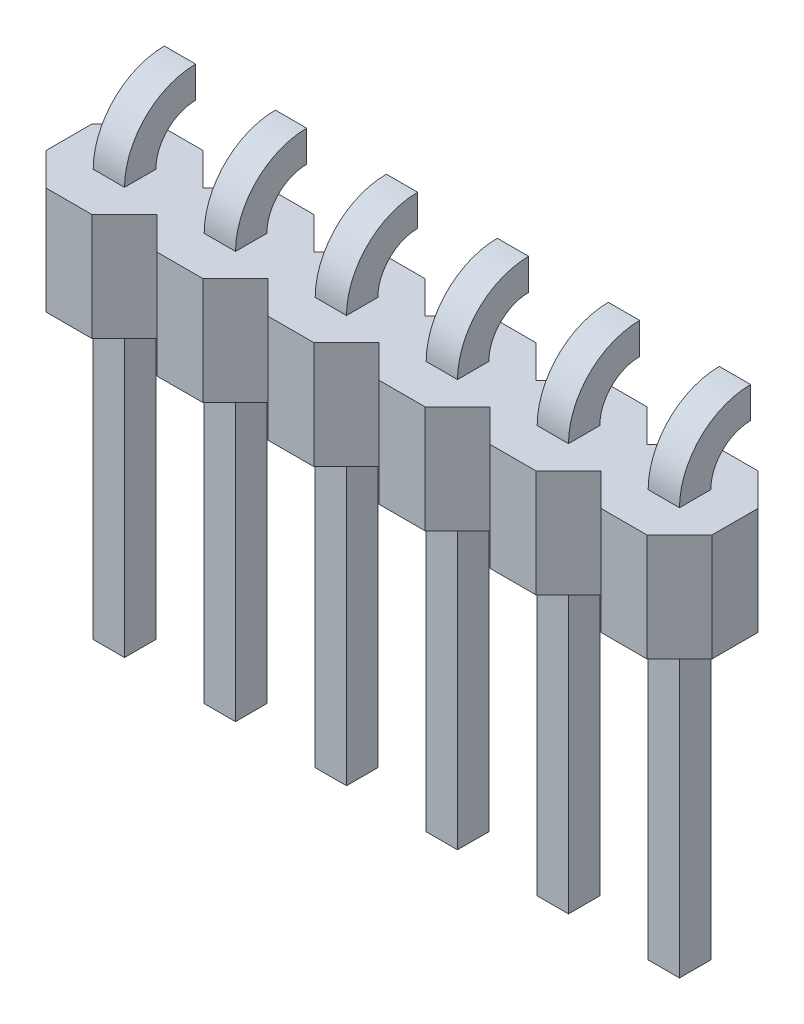
SolidWorks part; units mm, degrees
ref_plane "Front Plane" through (0, 0, 0) normal (0, 0, 1) x (1, 0, 0)
ref_plane "Top Plane" through (0, 0, 0) normal (0, 1, 0) x (1, 0, 0)
ref_plane "Right Plane" through (0, 0, 0) normal (1, 0, 0) x (0, 0, -1)
sketch "Sketch1" plane through (0, 0, 0) normal (0, 1, 0) x (1, 0, 0)
  line L0 (2.83, -0.35) -> (2.83, 0.35)
  line L1 (-0.35, -0.35) -> (0.35, -0.35)
  line L2 (-0.35, -0.35) -> (-0.35, 0.35)
  line L3 (-0.35, 0.35) -> (0.35, 0.35)
  line L4 (0.35, -0.35) -> (0.35, 0.35)
  line L5 (-0.35, -0.35) -> (0.35, 0.35) construction
  line L6 (-0.35, 0.35) -> (0.35, -0.35) construction
  line L7 (2.13, 0.35) -> (2.83, 0.35)
  line L8 (2.13, -0.35) -> (2.13, 0.35)
  line L9 (2.13, -0.35) -> (2.83, -0.35)
  line L10 (5.31, -0.35) -> (5.31, 0.35)
  line L11 (4.61, 0.35) -> (5.31, 0.35)
  line L12 (4.61, -0.35) -> (4.61, 0.35)
  line L13 (4.61, -0.35) -> (5.31, -0.35)
  line L14 (7.79, -0.35) -> (7.79, 0.35)
  line L15 (7.09, 0.35) -> (7.79, 0.35)
  line L16 (7.09, -0.35) -> (7.09, 0.35)
  line L17 (7.09, -0.35) -> (7.79, -0.35)
  line L18 (10.27, -0.35) -> (10.27, 0.35)
  line L19 (9.57, 0.35) -> (10.27, 0.35)
  line L20 (9.57, -0.35) -> (9.57, 0.35)
  line L21 (9.57, -0.35) -> (10.27, -0.35)
  line L22 (12.75, -0.35) -> (12.75, 0.35)
  line L23 (12.05, 0.35) -> (12.75, 0.35)
  line L24 (12.05, -0.35) -> (12.05, 0.35)
  line L25 (12.05, -0.35) -> (12.75, -0.35)
  point P0 (0, 0)
  dimension "D1" = 0.7
  dimension "D2" = 0.7
  dimension "D4" = 1.78
  dimension "D3" = 6
extrude "Boss-Extrude1" add sketch "Sketch1" along normal blind 9.1
sketch "Sketch3" plane through (0, 9.1, 0) normal (0, 1, 0) x (1, 0, 0)
  line L0 (-0.5136, 1.24) -> (-1.24, 0.5136)
  line L1 (-0.35, -0.35) -> (0.35, -0.35)
  line L2 (-0.35, -0.35) -> (-0.35, 0.35)
  line L3 (-0.35, 0.35) -> (0.35, 0.35)
  line L4 (0.35, -0.35) -> (0.35, 0.35)
  line L5 (-0.35, -0.35) -> (0.35, 0.35) construction
  line L6 (-0.35, 0.35) -> (0.35, -0.35) construction
  line L7 (-1.24, -0.5136) -> (-0.5136, -1.24)
  line L8 (-0.5136, -1.24) -> (0.5136, -1.24)
  line L9 (0.5136, -1.24) -> (1.24, -0.5136)
  line L10 (1.24, -0.5136) -> (1.24, 0.5136)
  line L11 (1.24, 0.5136) -> (0.5136, 1.24)
  line L12 (0.5136, 1.24) -> (-0.5136, 1.24)
  line L13 (-1.24, 0.5136) -> (-1.24, -0.5136)
  line L14 (2.83, 0.35) -> (2.13, -0.35) construction
  line L15 (2.83, -0.35) -> (2.13, 0.35) construction
  line L16 (3.72, -0.5136) -> (3.72, 0.5136)
  line L17 (2.9936, -1.24) -> (3.72, -0.5136)
  line L18 (2.83, 0.35) -> (2.13, 0.35)
  line L19 (2.13, 0.35) -> (2.13, -0.35)
  line L20 (2.13, -0.35) -> (2.83, -0.35)
  line L21 (2.83, -0.35) -> (2.83, 0.35)
  line L22 (2.83, 0.35) -> (2.13, 0.35) construction
  line L23 (2.13, 0.35) -> (2.13, -0.35) construction
  line L24 (2.13, -0.35) -> (2.83, -0.35) construction
  line L25 (2.83, -0.35) -> (2.83, 0.35) construction
  line L26 (1.9664, -1.24) -> (2.9936, -1.24)
  line L27 (1.24, -0.5136) -> (1.9664, -1.24)
  line L28 (1.24, 0.5136) -> (1.24, -0.5136)
  line L29 (1.9664, 1.24) -> (1.24, 0.5136)
  line L30 (2.9936, 1.24) -> (1.9664, 1.24)
  line L31 (3.72, 0.5136) -> (2.9936, 1.24)
  line L32 (6.2, -0.5136) -> (6.2, 0.5136)
  line L33 (5.4736, -1.24) -> (6.2, -0.5136)
  line L34 (4.4464, -1.24) -> (5.4736, -1.24)
  line L35 (3.72, -0.5136) -> (4.4464, -1.24)
  line L36 (3.72, 0.5136) -> (3.72, -0.5136)
  line L37 (4.4464, 1.24) -> (3.72, 0.5136)
  line L38 (5.4736, 1.24) -> (4.4464, 1.24)
  line L39 (6.2, 0.5136) -> (5.4736, 1.24)
  line L40 (8.68, -0.5136) -> (8.68, 0.5136)
  line L41 (7.9536, -1.24) -> (8.68, -0.5136)
  line L42 (6.9264, -1.24) -> (7.9536, -1.24)
  line L43 (6.2, -0.5136) -> (6.9264, -1.24)
  line L44 (6.2, 0.5136) -> (6.2, -0.5136)
  line L45 (6.9264, 1.24) -> (6.2, 0.5136)
  line L46 (7.9536, 1.24) -> (6.9264, 1.24)
  line L47 (8.68, 0.5136) -> (7.9536, 1.24)
  line L48 (11.16, -0.5136) -> (11.16, 0.5136)
  line L49 (10.4336, -1.24) -> (11.16, -0.5136)
  line L50 (9.4064, -1.24) -> (10.4336, -1.24)
  line L51 (8.68, -0.5136) -> (9.4064, -1.24)
  line L52 (8.68, 0.5136) -> (8.68, -0.5136)
  line L53 (9.4064, 1.24) -> (8.68, 0.5136)
  line L54 (10.4336, 1.24) -> (9.4064, 1.24)
  line L55 (11.16, 0.5136) -> (10.4336, 1.24)
  line L56 (13.64, -0.5136) -> (13.64, 0.5136)
  line L57 (12.9136, -1.24) -> (13.64, -0.5136)
  line L58 (11.8864, -1.24) -> (12.9136, -1.24)
  line L59 (11.16, -0.5136) -> (11.8864, -1.24)
  line L60 (11.16, 0.5136) -> (11.16, -0.5136)
  line L61 (11.8864, 1.24) -> (11.16, 0.5136)
  line L62 (12.9136, 1.24) -> (11.8864, 1.24)
  line L63 (13.64, 0.5136) -> (12.9136, 1.24)
  circle A0 centre (0, 0) radius 1.24 construction
  point P0 (0, 0)
  line M16 (12.75, 0.35) -> (12.05, 0.35)
  line M17 (12.05, 0.35) -> (12.05, -0.35)
  line M18 (12.05, -0.35) -> (12.75, -0.35)
  line M19 (12.75, -0.35) -> (12.75, 0.35)
  dimension "D1" = 0.7
  dimension "D2" = 0.7
  dimension "D4" = 1.24
  dimension "D3" = 0
  dimension "D5" = 6
extrude "Yükseklik-Ekstrüzyon1" add sketch "Sketch3" against normal blind 2.4 contours L56 L63 L62 L61 L48 L59 L58 L57 M16 M19 M18 M17 | L48 L55 L54 L53 L40 L51 L50 L49 | L40 L47 L46 L45 L32 L43 L42 L41 | L32 L39 L38 L37 L16 L35 L34 L33 | L16 L31 L30 L29 L10 L27 L26 L17 | L0 L13 L7 L8 L9 L10 L11 L12 L4 L1 L2 L3 region at (0, 9.1, -1.2049) region at (1.628, 9.1, -0.852) region at (4.96, 9.1, 0) region at (7.44, 9.1, 0) region at (9.92, 9.1, 0) region at (11.548, 9.1, -0.852)
sketch "Çizim1" plane through (0, 9.1, 0) normal (0, 1, 0) x (1, 0, 0)
  line L0 (10.27, 0.35) -> (9.57, 0.35)
  line L1 (10.27, -0.35) -> (10.27, 0.35)
  line L2 (9.57, -0.35) -> (10.27, -0.35)
  line L3 (9.57, 0.35) -> (9.57, -0.35)
  line L4 (12.75, 0.35) -> (12.05, 0.35)
  line L5 (12.75, -0.35) -> (12.75, 0.35)
  line L6 (12.05, -0.35) -> (12.75, -0.35)
  line L7 (12.05, 0.35) -> (12.05, -0.35)
  line L8 (12.75, 0.35) -> (12.05, 0.35)
  line L9 (12.75, -0.35) -> (12.75, 0.35)
  line L10 (12.05, -0.35) -> (12.75, -0.35)
  line L11 (12.05, 0.35) -> (12.05, -0.35)
  line L12 (7.79, 0.35) -> (7.09, 0.35)
  line L13 (7.79, -0.35) -> (7.79, 0.35)
  line L14 (7.09, -0.35) -> (7.79, -0.35)
  line L15 (7.09, 0.35) -> (7.09, -0.35)
  line L16 (5.31, 0.35) -> (4.61, 0.35)
  line L17 (5.31, -0.35) -> (5.31, 0.35)
  line L18 (4.61, -0.35) -> (5.31, -0.35)
  line L19 (4.61, 0.35) -> (4.61, -0.35)
  line L20 (2.83, 0.35) -> (2.13, 0.35)
  line L21 (2.83, -0.35) -> (2.83, 0.35)
  line L22 (2.13, -0.35) -> (2.83, -0.35)
  line L23 (2.13, 0.35) -> (2.13, -0.35)
  line L24 (0.35, 0.35) -> (-0.35, 0.35)
  line L25 (0.35, -0.35) -> (0.35, 0.35)
  line L26 (-0.35, -0.35) -> (0.35, -0.35)
  line L27 (-0.35, 0.35) -> (-0.35, -0.35)
  dimension "D1" = 0
  dimension "D2" = 6
revolve "Döndür1" add sketch "Çizim1" angle 90 about axis through (0, 9.1, -1.24) along (-1, 0, 0)
